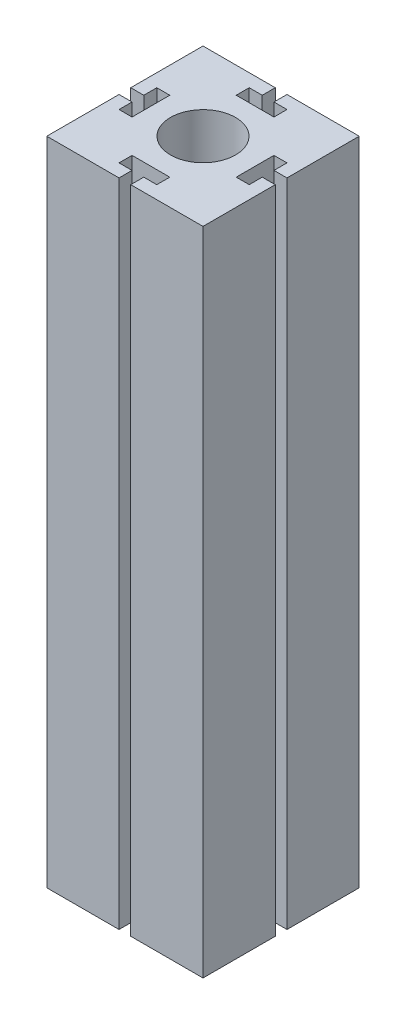
SolidWorks part; units mm, degrees
ref_plane "Plan de face" through (0, 0, 0) normal (0, 0, 1) x (1, 0, 0)
ref_plane "Plan de dessus" through (0, 0, 0) normal (0, 1, 0) x (1, 0, 0)
ref_plane "Plan de droite" through (0, 0, 0) normal (1, 0, 0) x (0, 0, -1)
sketch "Esquisse1" plane through (0, 0, 0) normal (0, 1, 0) x (1, 0, 0)
  line L1 (-6, 6) -> (6, 6)
  line L2 (-6, 6) -> (-6, -6)
  line L3 (-6, -6) -> (6, -6)
  line L4 (6, 6) -> (6, -6)
  dimension "D1" = 12
  dimension "D2" = 12
  dimension "D3" = 6
  dimension "D4" = 6
extrude "Boss.-Extru.1" add sketch "Esquisse1" along normal blind 50
sketch "Esquisse2" plane through (0, 50, 0) normal (0, 1, 0) x (1, 0, 0)
  line L0 (-5, -0.45) -> (-5, -1.45)
  line L1 (-6, 0.45) -> (-5, 0.45)
  line L2 (-6, 0.45) -> (-6, -0.45)
  line L3 (-6, -0.45) -> (-5, -0.45)
  line L5 (-5, 1.45) -> (-4, 1.45)
  line L6 (-5, 1.45) -> (-5, 0.45)
  line L7 (-5, -1.45) -> (-4, -1.45)
  line L8 (-4, 1.45) -> (-4, -1.45)
  line L9 (-6, 6) -> (-6, -6) construction
  line L10 (1.45, 5) -> (1.45, 4)
  line L11 (1.45, 4) -> (-1.45, 4)
  line L12 (-1.45, 5) -> (-1.45, 4)
  line L13 (-0.45, 5) -> (-1.45, 5)
  line L14 (-0.45, 6) -> (-0.45, 5)
  line L15 (0.45, 6) -> (-0.45, 6)
  line L16 (0.45, 6) -> (0.45, 5)
  line L17 (1.45, 5) -> (0.45, 5)
  line L18 (5, -1.45) -> (4, -1.45)
  line L19 (4, -1.45) -> (4, 1.45)
  line L20 (5, 1.45) -> (4, 1.45)
  line L21 (5, 0.45) -> (5, 1.45)
  line L22 (6, 0.45) -> (5, 0.45)
  line L23 (6, -0.45) -> (6, 0.45)
  line L24 (6, -0.45) -> (5, -0.45)
  line L25 (5, -1.45) -> (5, -0.45)
  line L26 (-1.45, -5) -> (-1.45, -4)
  line L27 (-1.45, -4) -> (1.45, -4)
  line L28 (1.45, -5) -> (1.45, -4)
  line L29 (0.45, -5) -> (1.45, -5)
  line L30 (0.45, -6) -> (0.45, -5)
  line L31 (-0.45, -6) -> (0.45, -6)
  line L32 (-0.45, -6) -> (-0.45, -5)
  line L33 (-1.45, -5) -> (-0.45, -5)
  point P38 (0, 0)
  dimension "D1" = 0.9
  dimension "D2" = 1
  dimension "D3" = 1
  dimension "D4" = 0
  dimension "D5" = 0.45
  dimension "D6" = 1
  dimension "D7" = 2
  dimension "D8" = 4
extrude "Enlèv. mat.-Extru.1" cut sketch "Esquisse2" against normal up to vertex (50 mm away) up to point (0, 0, 0)
sketch "Esquisse3" plane through (0, 50, 0) normal (0, 1, 0) x (1, 0, 0)
  circle A0 centre (0, 0) radius 2.5
  dimension "D1" = 5
extrude "Enlèv. mat.-Extru.2" cut sketch "Esquisse3" against normal blind 45
sketch "Esquisse4" plane through (0, 5, 0) normal (0, 1, 0) x (1, 0, 0)
  circle A0 centre (0, 0) radius 1
  dimension "D1" = 2
extrude "Enlèv. mat.-Extru.3" cut sketch "Esquisse4" against normal up to surface (5 mm away) up to face at (0, 0, 0)
chamfer "Chanfrein1" distance 2 distance2 2 1 edges at (0, 5, 1)
